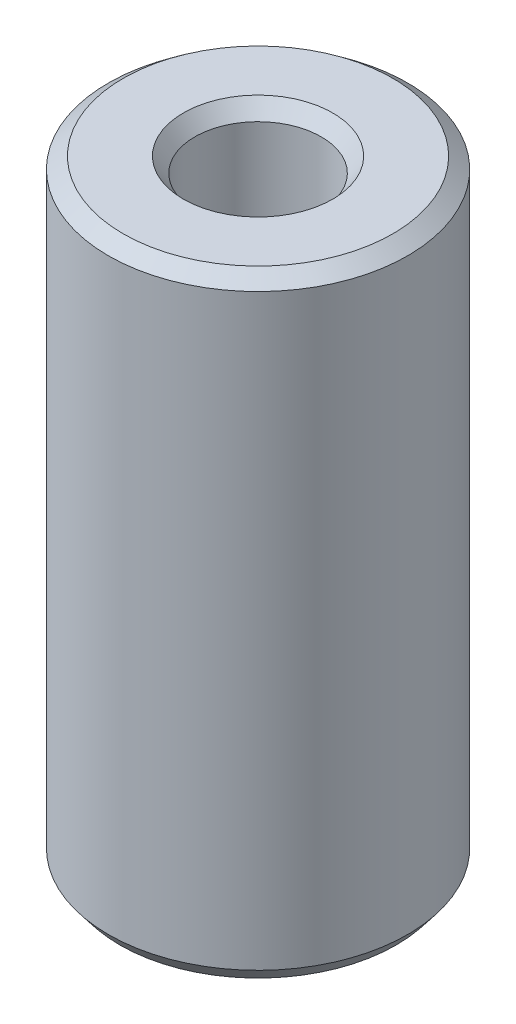
SolidWorks part; units mm, degrees
ref_plane "Front Plane" through (0, 0, 0) normal (0, 0, 1) x (1, 0, 0)
ref_plane "Top Plane" through (0, 0, 0) normal (0, 1, 0) x (1, 0, 0)
ref_plane "Right Plane" through (0, 0, 0) normal (1, 0, 0) x (0, 0, -1)
sketch "Sketch1" plane through (0, 0, 0) normal (0, 1, 0) x (1, 0, 0)
  circle A0 centre (0, 0) radius 47.5
  dimension "SLEEVE_OD" = 95
extrude "Boss-Extrude1" add sketch "Sketch1" along normal blind 194.9333
sketch "Sketch2" plane through (0, 0, 0) normal (0, 1, 0) x (1, 0, 0)
  circle A0 centre (0, 0) radius 20.0499
  dimension "BORE_D" = 40.0999
extrude "Cut-Extrude1" cut sketch "Sketch2" along normal through all
chamfer "Chamfer1" distance 3.6611 angle 52.24 4 edges at (0, 194.9333, 20.0499) (0, 0, 20.0499) (0, 0, 47.5) (0, 194.9333, 47.5) first distance on face at (0, 194.9333, 20.0499) first distance on face at (0, 0, 20.0499) first distance on face at (0, 194.9333, 47.5)
